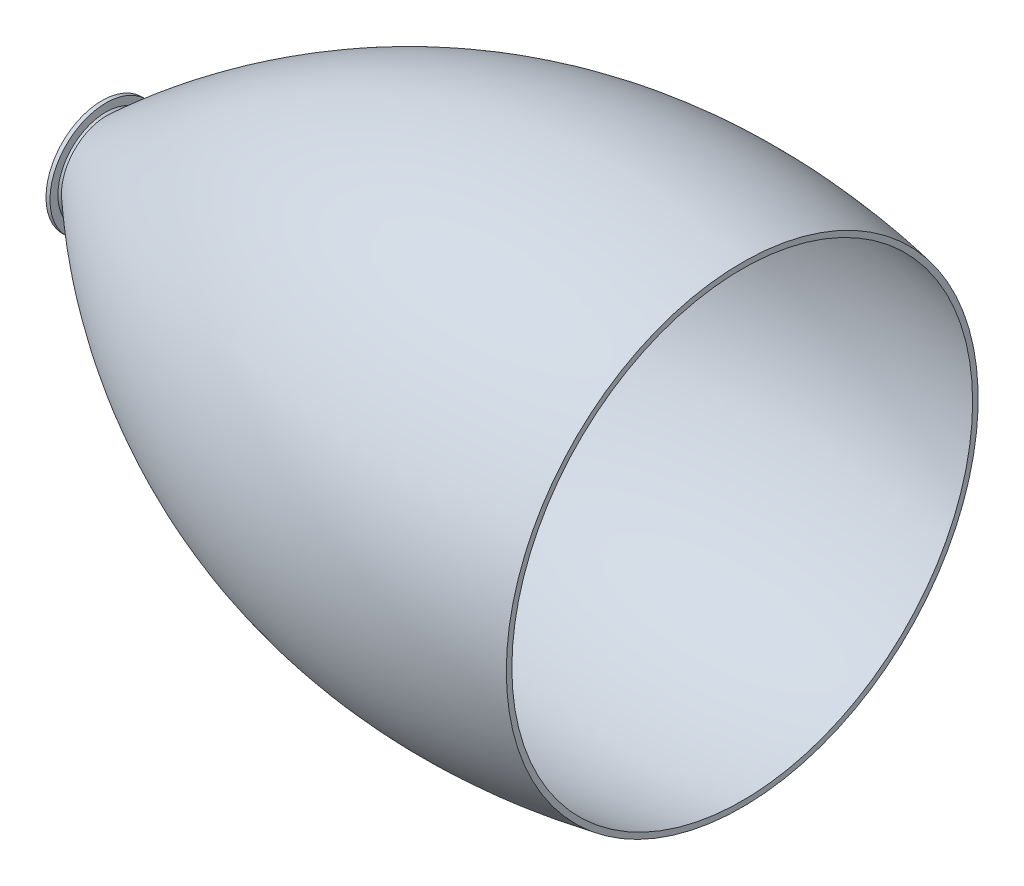
SolidWorks part; units mm, degrees
material "A286 Iron Base Superalloy"
ref_plane "Front Plane" through (0, 0, 0) normal (0, 0, 1) x (1, 0, 0)
ref_plane "Top Plane" through (0, 0, 0) normal (0, 1, 0) x (1, 0, 0)
ref_plane "Right Plane" through (0, 0, 0) normal (1, 0, 0) x (0, 0, -1)
sketch "Sketch1" plane through (0, 0, 0) normal (0, 0, 1) x (1, 0, 0)
  line L0 (-1229.8282, 0) -> (1426.3964, 0) construction
  line L1 (0, -63.5) -> (0, 63.5) construction
  line L2 (0, 0) -> (1016, 0) construction
  line L3 (1016, -368.3) -> (1016, 368.3) construction
  line L5 (1016, 377.19) -> (1016, 368.3)
  line L6 (0, -72.39) -> (0, -63.5)
  line L7 (1016, -377.19) -> (1016, -368.3)
  line L8 (-412.8242, -144.8099) -> (-412.8242, 144.8099) construction
  line L9 (-412.8242, 144.8099) -> (-412.8242, 153.6999)
  line L10 (-412.8242, -144.8099) -> (-412.8242, -153.6999)
  spline S0 degree 2 poles (0, 63.5) (448.5492, 461.9788) (1016, 368.3) knots 0 0 0 1 1 1
  spline S1 degree 2 poles (0, -63.5) (448.5492, -461.9788) (1016, -368.3) knots 0 0 0 1 1 1
  spline S2 degree 2 poles (0, -72.39) (446.4179, -483.3057) (1016, -377.19) knots 0 0 0 1 1 1
  spline S3 degree 2 poles (0, -63.5) (448.5492, -461.9788) (1016, -368.3) knots 0 0 0 1 1 1
  spline S4 degree 2 poles (0, 72.39) (446.4179, 483.3057) (1016, 377.19) knots 0 0 0 1 1 1
  spline S5 degree 2 poles (0, 63.5) (-192.2835, 162.6782) (-412.8242, 144.8099) knots 0 0 0 1 1 1
  spline S6 degree 2 poles (0, -63.5) (-192.2835, -162.6782) (-412.8242, -144.8099) knots 0 0 0 1 1 1
  spline S7 degree 2 poles (0, -72.39) (-189.3535, -181.7828) (-412.8242, -153.6999) knots 0 0 0 1 1 1
  spline S9 degree 2 poles (0, 72.39) (-189.3535, 181.7828) (-412.8242, 153.6999) knots 0 0 0 1 1 1
  point P8 (0, 0)
  point P14 (1016, 0)
  point P22 (-412.8242, 0)
  point P23 (595.566, 367.2761)
  point P27 (595.566, 382.2422)
  dimension "D4" = 8.89
  dimension "D1" = 127
  dimension "D2" = 1016
  dimension "D3" = 736.6
  dimension "D5" = 8.89
  dimension "D6" = 8.89
  dimension "D7" = 289.6197
revolve "Revolve3" add sketch "Sketch1" angle 360 about L0 region at (1001.3232, 372.745, 0)
ref_plane "Plane1" through (0, 0, 0) normal (1, 0, 0) x (0, 0, -1)
ref_plane "Plane2" through (-7.62, 0, 0) normal (-1, 0, 0) x (0, 0, 1)
sketch "Sketch4" plane through (-7.62, 0, 0) normal (-1, 0, 0) x (0, 0, 1)
  line L1 (-1213.2286, 638.9142) -> (1085.9115, 638.9142)
  line L2 (-1213.2286, 638.9142) -> (-1213.2286, -445.9528)
  line L3 (-1213.2286, -445.9528) -> (1085.9115, -445.9528)
  line L4 (1085.9115, 638.9142) -> (1085.9115, -445.9528)
extrude "Cut-Extrude1" cut sketch "Sketch4" along normal blind 554.228
sketch "Sketch5" plane through (-7.62, 0, 0) normal (-1, 0, 0) x (0, 0, 1)
  circle A0 centre (0, 0) radius 89.4288
  circle A1 centre (0, 0) radius 76.7288 construction
  circle A2 centre (0, 0) radius 76.7288
  dimension "D1" = 12.7
extrude "Boss-Extrude1" add sketch "Sketch5" against normal blind 6.35 separate body
